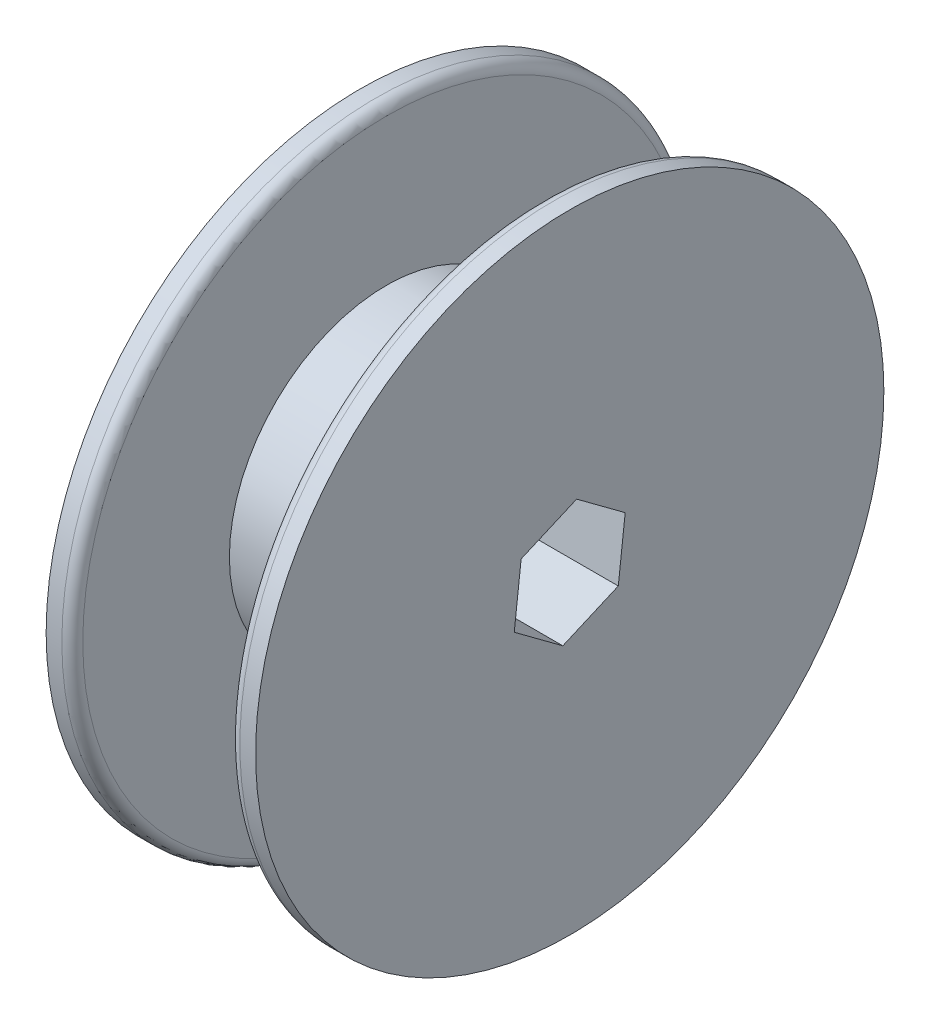
SolidWorks part; units mm, degrees
ref_plane "Front" through (0, 0, 0) normal (0, 0, 1) x (1, 0, 0)
ref_plane "Top" through (0, 0, 0) normal (0, 1, 0) x (1, 0, 0)
ref_plane "Right" through (0, 0, 0) normal (1, 0, 0) x (0, 0, -1)
sketch "Sketch1" plane through (0, 0, 0) normal (1, 0, 0) x (0, 0, -1)
  circle A0 centre (0, 0) radius 19.05
  dimension "D1" = 38.1
extrude "Boss-Extrude1" add sketch "Sketch1" along normal blind 19.05
sketch "Sketch2" plane through (0, 0, 0) normal (-1, 0, 0) x (0, 0, 1)
  circle A0 centre (0, 0) radius 38.1
  circle A1 centre (0, 0) radius 19.05 construction
  dimension "D1" = 19.05
extrude "Boss-Extrude2" add sketch "Sketch2" along normal blind 3.175
sketch "Sketch3" plane through (19.05, 0, 0) normal (1, 0, 0) x (0, 0, -1)
  circle A0 centre (0, 0) radius 38.1 construction
  circle A1 centre (0, 0) radius 38.1
extrude "Boss-Extrude3" add sketch "Sketch3" along normal blind 3.175
sketch "Sketch4" plane through (-3.175, 0, 0) normal (-1, 0, 0) x (0, 0, 1)
  circle A0 centre (0, 0) radius 6.35
  dimension "D1" = 12.7
extrude "Cut-Extrude1" cut sketch "Sketch4" against normal through all
fillet "Fillet1" radius 1.27 2 edges at (0, 0, 38.1) (19.05, 0, -38.1)
sketch "Sketch5" plane through (-3.175, 0, 0) normal (-1, 0, 0) x (0, 0, 1)
  line L1 (-5.8904, -4.3666) -> (0.8364, -7.2845)
  line L2 (0.8364, -7.2845) -> (6.7268, -2.9179)
  line L3 (6.7268, -2.9179) -> (5.8904, 4.3666)
  line L4 (5.8904, 4.3666) -> (-0.8364, 7.2845)
  line L5 (-0.8364, 7.2845) -> (-6.7268, 2.9179)
  line L6 (-6.7268, 2.9179) -> (-5.8904, -4.3666)
  circle A0 centre (0, 0) radius 6.35 construction
extrude "Cut-Extrude2" cut sketch "Sketch5" against normal through all
